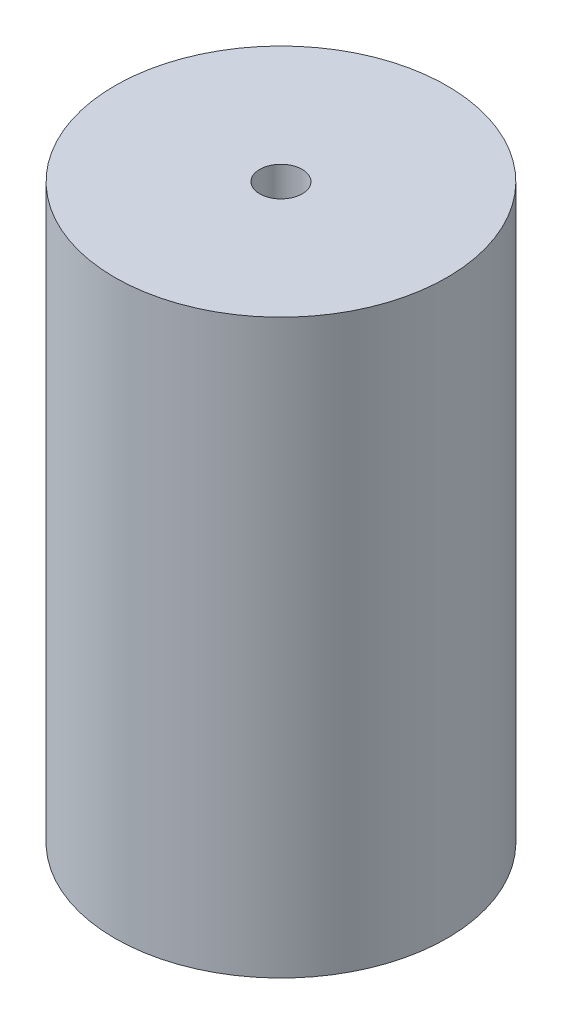
SolidWorks part; units mm, degrees
material "Acrylic (Medium-high impact)"
ref_plane "Front Plane" through (0, 0, 0) normal (0, 0, 1) x (1, 0, 0)
ref_plane "Top Plane" through (0, 0, 0) normal (0, 1, 0) x (1, 0, 0)
ref_plane "Right Plane" through (0, 0, 0) normal (1, 0, 0) x (0, 0, -1)
sketch "Sketch1" plane through (0, 0, 0) normal (0, 1, 0) x (1, 0, 0)
  circle A0 centre (0, 0) radius 63.5
  circle A1 centre (0, 0) radius 69.85
  dimension "D1" = 127
  dimension "D2" = 6.35
extrude "Boss-Extrude1" add sketch "Sketch1" along normal blind 12.7 contours A1
extrude "Boss-Extrude2" add sketch "Sketch1<3>" along normal blind 227.965
sketch "Sketch1<3>" plane through (0, 0, 0) normal (0, 1, 0) x (1, 0, 0) same geometry as "Sketch1"
sketch "Sketch2" plane through (0, 227.965, 0) normal (0, 1, 0) x (1, 0, 0)
  circle A1 centre (0, 0) radius 69.85
  circle A2 centre (0, 0) radius 69.85
  dimension "D1" = 0
extrude "Boss-Extrude3" add sketch "Sketch2" along normal blind 12.7
sketch "Sketch3" plane through (0, 240.665, 0) normal (0, 1, 0) x (1, 0, 0)
  circle A0 centre (0, 0) radius 8.9297
  dimension "D1" = 17.8594
extrude "Cut-Extrude1" cut sketch "Sketch3" against normal blind 335.534
